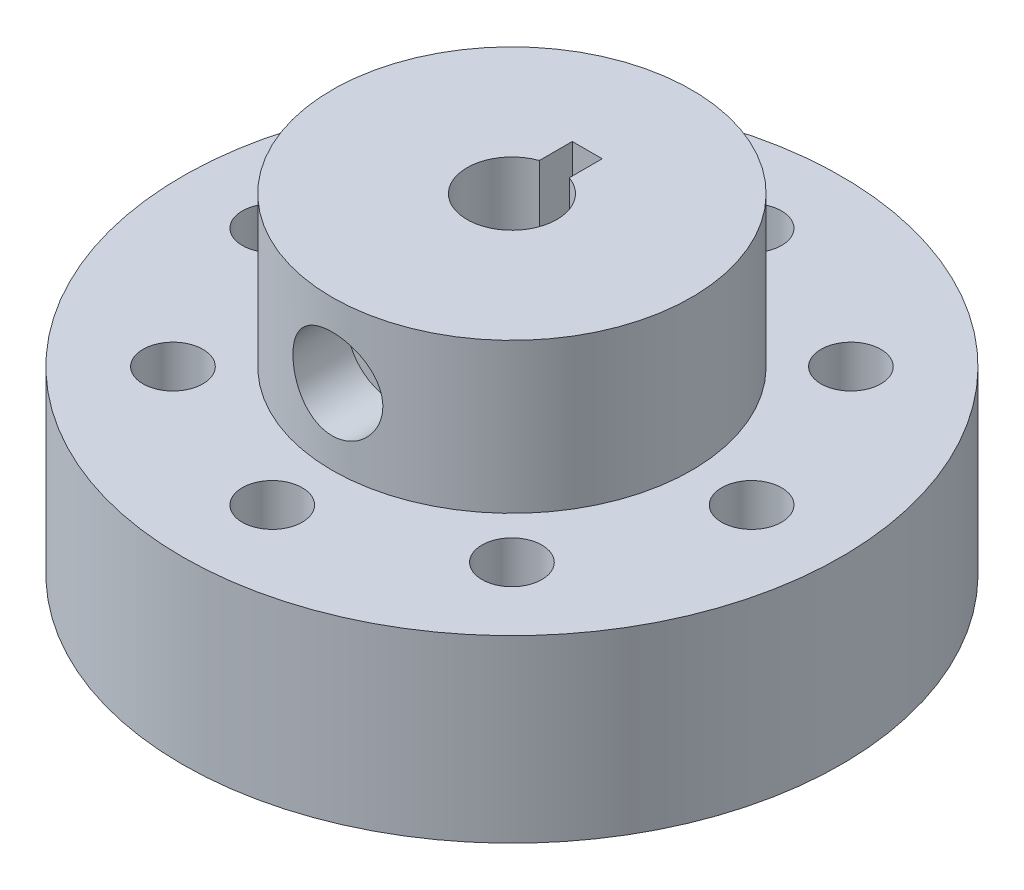
SolidWorks part; units mm, degrees
material "1060 Alloy"
ref_plane "Front Plane" through (0, 0, 0) normal (0, 0, 1) x (1, 0, 0)
ref_plane "Top Plane" through (0, 0, 0) normal (0, 1, 0) x (1, 0, 0)
ref_plane "Right Plane" through (0, 0, 0) normal (1, 0, 0) x (0, 0, -1)
sketch "Sketch1" plane through (0, 0, 0) normal (0, 1, 0) x (1, 0, 0)
  circle A0 centre (0, 0) radius 11
  circle A1 centre (0, 0) radius 8 construction
  circle A2 centre (0, 8) radius 1
  circle A3 centre (5.6569, 5.6569) radius 1
  circle A4 centre (8, 0) radius 1
  circle A5 centre (5.6569, -5.6569) radius 1
  circle A6 centre (0, -8) radius 1
  circle A7 centre (-5.6569, -5.6569) radius 1
  circle A8 centre (-8, 0) radius 1
  circle A9 centre (-5.6569, 5.6569) radius 1
  point P22 (0, 0)
  dimension "D1" = 22
  dimension "D2" = 16
  dimension "D3" = 2
  dimension "D4" = 8
extrude "Boss-Extrude1" add sketch "Sketch1" along normal blind 6
sketch "Sketch2" plane through (0, 0, 0) normal (0, -1, 0) x (1, 0, 0)
  circle A0 centre (0, 0) radius 4
  dimension "D1" = 8
extrude "Cut-Extrude1" cut sketch "Sketch2" against normal blind 5.5
sketch "Sketch3" plane through (0, 6, 0) normal (0, 1, 0) x (1, 0, 0)
  line L0 (-0.5, 1.4142) -> (0.5, 1.4142)
  line L1 (-0.5, 1.4142) -> (-0.5, 2.5142)
  line L2 (0.5, 1.4142) -> (0.5, 2.5142)
  line L3 (-0.5, 2.5142) -> (0.5, 2.5142)
  circle A0 centre (0, 0) radius 6
  circle A1 centre (0, 0) radius 1.5
  dimension "D1" = 12
  dimension "D4" = 3
  dimension "D2" = 1.1
  dimension "D3" = 1
extrude "Boss-Extrude2" add sketch "Sketch3" along normal blind 5 contours A0 A1 L1 L3 L2 region at (-5.8303, 6, 0)
ref_plane "Plane1" through (0, 0, 6) normal (0, 0, 1) x (1, 0, 0)
sketch "Sketch6" plane through (0, 0, 6) normal (0, 0, 1) x (1, 0, 0)
  line L0 (0, 11) -> (0, 0) construction
  line L1 (6, 11) -> (-6, 11) construction
  line L2 (-11, 0) -> (11, 0) construction
  line L3 (-6, 8.5) -> (6, 8.5) construction
  line L4 (-6, 11) -> (-6, 6) construction
  line L5 (6, 6) -> (6, 11) construction
  circle A0 centre (0, 8.5) radius 1.5
  circle A1 centre (0, 8.5) radius 1
  dimension "D1" = 3
  dimension "D2" = 2
extrude "Cut-Extrude2" cut sketch "Sketch6" against normal blind 6 contours A1 region at (0, 8.5, 6)
extrude "Cut-Extrude3" cut sketch "Sketch6<3>" against normal blind 2
sketch "Sketch6<3>" plane through (0, 0, 6) normal (0, 0, 1) x (1, 0, 0) same geometry as "Sketch6"
